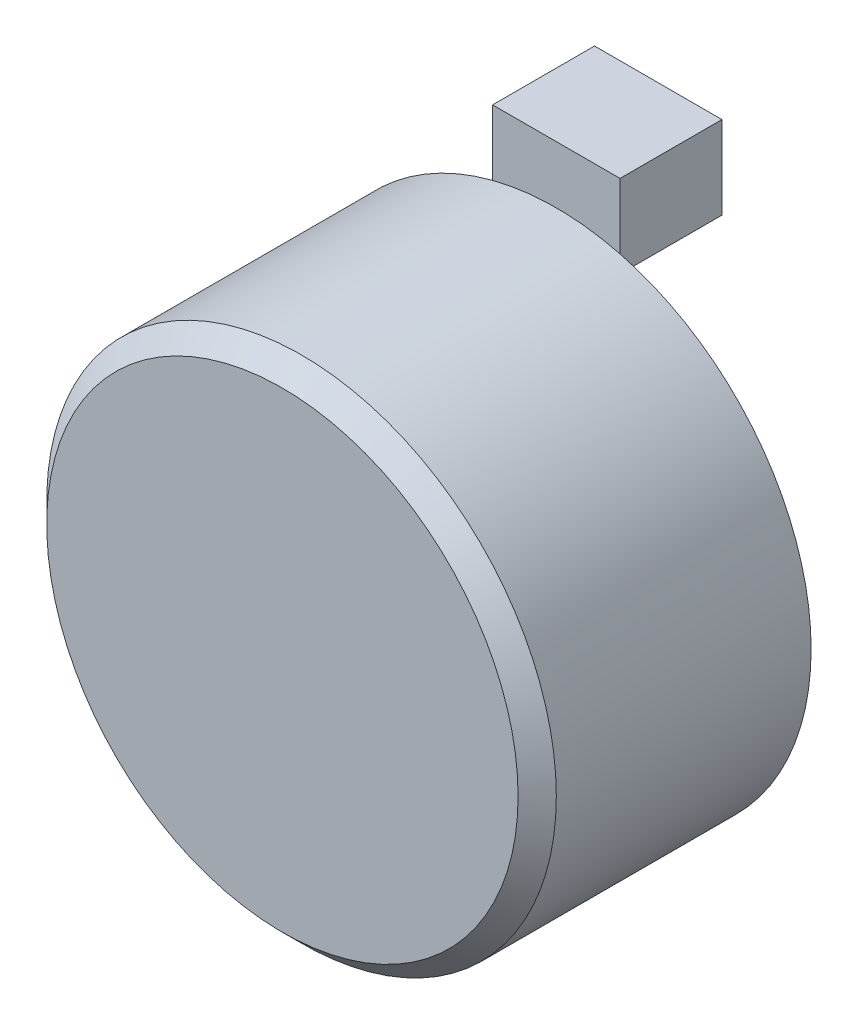
SolidWorks part; units mm, degrees
ref_plane "Front Plane" through (0, 0, 0) normal (0, 0, 1) x (1, 0, 0)
ref_plane "Top Plane" through (0, 0, 0) normal (0, 1, 0) x (1, 0, 0)
ref_plane "Right Plane" through (0, 0, 0) normal (1, 0, 0) x (0, 0, -1)
sketch "SK_Body" plane through (0, 0, 0) normal (0, 1, 0) x (1, 0, 0)
  line L0 (0, -10) -> (0, 53) construction
  line L1 (0, 0) -> (37, 0)
  line L2 (37, 0) -> (40, 3)
  line L3 (40, 3) -> (40, 43)
  line L4 (40, 43) -> (37, 43)
  line L5 (37, 43) -> (0, 43)
  line L6 (0, 43) -> (0, 0)
  dimension "P1" = 10
  dimension "P2" = 53
  dimension "R_front" = 37
  dimension "P4" = 40
  dimension "P5" = 3
  dimension "R_body" = 40
  dimension "L_body" = 43
  dimension "P8" = 37
  dimension "P9" = 43
  dimension "P10" = 43
revolve "Housing_Body" add sketch "SK_Body" angle 360 about L0
ref_plane "PL_Rear" through (0, 0, -43) normal (0, 0, 1) x (1, 0, 0)
sketch "SK_RearHole" plane through (0, 0, -43) normal (0, 0, 1) x (1, 0, 0)
  circle A0 centre (34, 0) radius 1.25
  dimension "D_rh" = 2.5
  dimension "R_rh" = 34
extrude "Rear_Tapped_Hole" cut sketch "SK_RearHole" along normal blind 8
ref_axis "AX_Joint" through (0, 0, -61.95) along (0, 0, 1)
pattern_circular "Rear_Hole_Pattern" count 6 over 360 about axis through (0, 0, -61.95) along (0, 0, 1) of "Rear_Tapped_Hole"
sketch "SK_Connector" plane through (0, 0, -43) normal (0, 0, 1) x (1, 0, 0)
  line L0 (-10, 36) -> (10, 36)
  line L1 (10, 36) -> (10, 49)
  line L2 (10, 49) -> (-10, 49)
  line L3 (-10, 49) -> (-10, 36)
  dimension "P1" = 10
  dimension "P2" = 36
  dimension "P3" = 10
  dimension "P4" = 36
  dimension "P5" = 10
  dimension "P6" = 49
  dimension "P7" = 10
  dimension "P8" = 49
extrude "Connector_Zone" add sketch "SK_Connector" against normal blind 16
equation "\"D_act\" = 80"
equation "\"L_housing\" = 43"
equation "\"PCD_rear\" = 68"
equation "\"D_rear_hole\" = 2.5"
equation "\"D_bearing_boss\" = 48"
equation "\"R_front@SK_Body\" = \"D_act\"/2-3.0"
equation "\"R_body@SK_Body\" = \"D_act\"/2"
equation "\"L_body@SK_Body\" = \"L_housing\""
equation "\"D_rh@SK_RearHole\" = \"D_rear_hole\""
equation "\"R_rh@SK_RearHole\" = \"PCD_rear\"/2"
